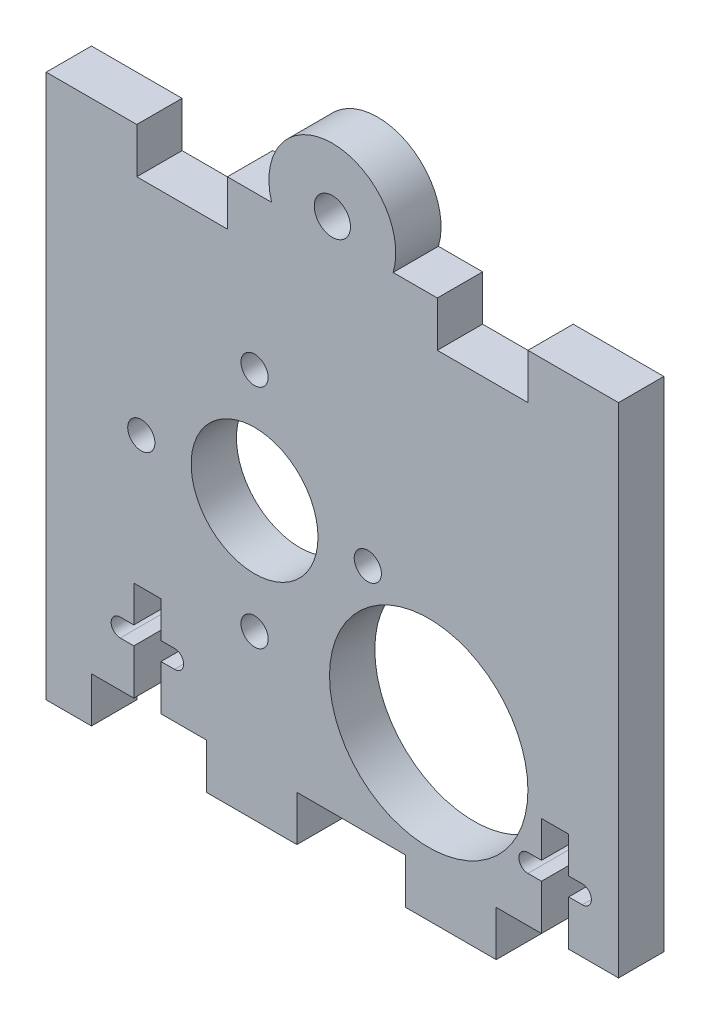
SolidWorks part; units mm, degrees
ref_plane "Front Plane" through (0, 0, 0) normal (0, 0, 1) x (1, 0, 0)
ref_plane "Top Plane" through (0, 0, 0) normal (0, 1, 0) x (1, 0, 0)
ref_plane "Right Plane" through (0, 0, 0) normal (1, 0, 0) x (0, 0, -1)
sketch "Sketch8" plane through (0, 0, 0) normal (0, 0, 1) x (1, 0, 0)
  line L0 (-31.586, -24.275) -> (31.586, -24.275)
  line L1 (-31.586, -24.275) -> (-31.586, 30.725)
  line L2 (-31.586, 30.725) -> (-8.414, 30.725)
  line L3 (31.586, -24.275) -> (31.586, -9.275)
  line L4 (27.586, -18.275) -> (21.586, -18.275) construction
  line L5 (31.586, -24.275) -> (21.586, -24.275)
  line L6 (26.086, -24.275) -> (23.086, -24.275)
  line L7 (26.086, -24.275) -> (26.086, -13.275)
  line L8 (26.086, -13.275) -> (23.086, -13.275)
  line L9 (23.086, -24.275) -> (23.086, -13.275)
  line L10 (27.586, -19.275) -> (21.586, -19.275)
  line L11 (27.586, -17.275) -> (21.586, -17.275)
  line L12 (24.586, -13.275) -> (24.586, -18.275) construction
  line L13 (24.586, -18.275) -> (24.586, -24.275) construction
  line L14 (-18.914, -24.275) -> (-21.914, -24.275)
  line L15 (-18.914, -24.275) -> (-18.914, -13.275)
  line L16 (-18.914, -13.275) -> (-21.914, -13.275)
  line L17 (-21.914, -24.275) -> (-21.914, -13.275)
  line L18 (-20.414, -13.275) -> (-20.414, -18.275) construction
  line L19 (-20.414, -18.275) -> (-20.414, -24.275) construction
  line L20 (-17.414, -18.275) -> (-23.414, -18.275) construction
  line L21 (-17.414, -19.275) -> (-23.414, -19.275)
  line L22 (-17.414, -17.275) -> (-23.414, -17.275)
  line L23 (-17.414, 24.725) -> (-23.414, 24.725) construction
  line L24 (-17.414, 25.725) -> (-23.414, 25.725)
  line L25 (-17.414, 23.725) -> (-23.414, 23.725)
  line L26 (-20.414, 24.725) -> (-20.414, 30.725) construction
  line L27 (-20.414, 19.725) -> (-20.414, 24.725) construction
  line L28 (-21.914, 30.725) -> (-21.914, 19.725)
  line L29 (-18.914, 19.725) -> (-21.914, 19.725)
  line L30 (-18.914, 30.725) -> (-18.914, 19.725)
  line L31 (-18.914, 30.725) -> (-21.914, 30.725)
  circle A0 centre (-8.586, 1.275) radius 7
  circle A1 centre (10.636, -11.325) radius 10.95
  circle A2 centre (-8.586, 13.775) radius 1.5
  circle A3 centre (3.914, 1.275) radius 1.5
  circle A4 centre (-8.586, -11.225) radius 1.5
  circle A5 centre (-21.086, 1.275) radius 1.5
  arc A6 (-8.414, 30.725) -> (31.586, -9.275) centre (-8.414, -9.275) cw
  arc A7 (27.586, -19.275) -> (27.586, -17.275) centre (27.586, -18.275) ccw
  arc A8 (21.586, -17.275) -> (21.586, -19.275) centre (21.586, -18.275) ccw
  arc A9 (-17.414, -19.275) -> (-17.414, -17.275) centre (-17.414, -18.275) ccw
  arc A10 (-23.414, -17.275) -> (-23.414, -19.275) centre (-23.414, -18.275) ccw
  arc A11 (-17.414, 25.725) -> (-17.414, 23.725) centre (-17.414, 24.725) cw
  arc A12 (-23.414, 23.725) -> (-23.414, 25.725) centre (-23.414, 24.725) cw
  point P25 (24.586, -18.275)
  point P41 (-20.414, -18.275)
  point P51 (-20.414, 24.725)
  dimension "D1" = 14
  dimension "D2" = 40
  dimension "D3" = 3
  dimension "D4" = 11
  dimension "D5" = 2
  dimension "D6" = 8
  dimension "D7" = 5
  dimension "D8" = 55
extrude "Boss-Extrude1" add sketch "Sketch8" along normal blind 5 contours L25 A12 L24 L28 L2 L1 L0 L17 L21 A10 L22 L16 L15 A9 L9 L10 A8 L11 L8 L7 A7 L3 A6 L30 A11 L29 A5 A4 A3 A2 region at (-30.7484, 3.225, 0)
sketch "Sketch9" plane through (0, 0, 0) normal (0, 0, -1) x (-1, 0, 0)
  line L0 (18.914, -24.275) -> (-23.086, -24.275) construction
  line L1 (-18.086, -24.275) -> (-8.086, -24.275)
  line L2 (-18.086, -24.275) -> (-18.086, -29.275)
  line L3 (-18.086, -29.275) -> (-8.086, -29.275)
  line L4 (-8.086, -24.275) -> (-8.086, -29.275)
  line L5 (-23.086, -24.275) -> (-23.086, -19.275) construction
  line L6 (3.914, -24.275) -> (3.914, -29.275)
  line L7 (3.914, -24.275) -> (13.914, -24.275)
  line L8 (13.914, -24.275) -> (13.914, -29.275)
  line L9 (3.914, -29.275) -> (13.914, -29.275)
  line L10 (18.914, -24.275) -> (18.914, -19.275) construction
  line L11 (-31.586, -24.275) -> (-31.586, -9.275) construction
  line L12 (31.586, 30.725) -> (-31.586, 30.725)
  line L13 (31.586, 30.725) -> (31.586, 11.7466)
  line L14 (31.586, 11.7466) -> (10.7623, 11.7466)
  line L15 (-31.586, 30.725) -> (-31.586, 11.7466)
  line L16 (6.4097, 11.7466) -> (-17.7432, 11.7466)
  line L19 (-31.586, 11.7466) -> (-31.586, -2.995)
  line L20 (31.586, -24.275) -> (26.586, -24.275)
  line L21 (31.586, -24.275) -> (31.586, -29.275)
  line L22 (31.586, -29.275) -> (26.586, -29.275)
  line L23 (26.586, -24.275) -> (26.586, -29.275)
  line L24 (-26.161, -2.995) -> (-17.7432, -2.995)
  line L25 (-17.7432, 11.7466) -> (-17.7432, -2.995)
  line L26 (-31.586, -9.275) -> (-26.161, -9.275)
  line L27 (-31.586, -9.275) -> (-31.586, -2.995)
  line L29 (-26.161, -9.275) -> (-26.161, -2.995)
  arc A0 (10.7623, 11.7466) -> (6.4097, 11.7466) centre (8.586, 13.775) ccw
  circle A1 centre (-10.636, -11.325) radius 10.95 construction
  dimension "D1" = 5
  dimension "D2" = 5
  dimension "D3" = 10
  dimension "D5" = 5
  dimension "D10" = 5
  dimension "D4" = 2
extrude "Boss-Extrude2" add sketch "Sketch9" against normal blind 5
sketch "Sketch10" plane through (0, 0, 0) normal (0, 0, -1) x (-1, 0, 0)
  arc A0 (0.2424, -12.5751) -> (-7.4428, -0.8509) centre (8.586, 1.275) ccw
  arc A1 (0.2424, -12.5751) -> (-7.4428, -0.8509) centre (-10.636, -11.325) ccw
extrude "Boss-Extrude3" [suppressed] add sketch "Sketch10" against normal blind 5
sketch "Sketch11" plane through (0, 0, 5) normal (0, 0, 1) x (1, 0, 0)
  line L0 (-31.586, 30.725) -> (31.586, 30.725) construction
  line L1 (-21.586, 30.725) -> (-11.586, 30.725)
  line L2 (-21.586, 30.725) -> (-21.586, 25.725)
  line L3 (-21.586, 25.725) -> (-11.586, 25.725)
  line L4 (-11.586, 30.725) -> (-11.586, 25.725)
  line L5 (-31.586, -29.275) -> (-31.586, 30.725) construction
  line L6 (21.586, 30.725) -> (11.586, 30.725)
  line L7 (21.586, 30.725) -> (21.586, 25.725)
  line L8 (21.586, 25.725) -> (11.586, 25.725)
  line L9 (11.586, 30.725) -> (11.586, 25.725)
  line L10 (31.586, -24.275) -> (31.586, 30.725) construction
  line L11 (-11.586, 32.725) -> (11.586, 32.725) construction
  circle A0 centre (0, 32.725) radius 2
  circle A1 centre (0, 32.725) radius 7
  line M2 (31.586, 30.725) -> (-31.586, 30.725)
  dimension "D5" = 4
  dimension "D1" = 5
  dimension "D2" = 10
  dimension "D3" = 10
  dimension "D4" = 10
  dimension "D6" = 5
extrude "Boss-Extrude4" add sketch "Sketch11" against normal blind 5
extrude "Cut-Extrude1" cut sketch "Sketch11<2>" against normal blind 5 contours L4 L2 L3 M2 | L9 L8 L7 M2 region at (16.586, 28.225, 5) region at (-16.586, 28.225, 5)
sketch "Sketch11<2>" plane through (0, 0, 5) normal (0, 0, 1) x (1, 0, 0) same geometry as "Sketch11"
